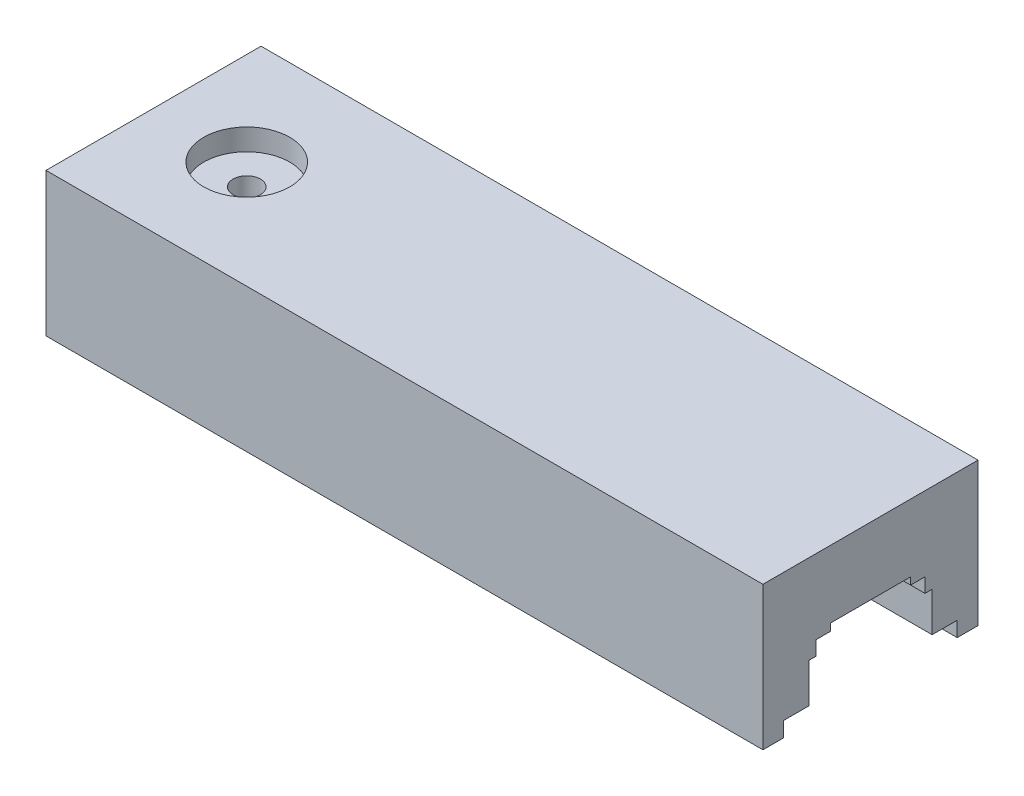
SolidWorks part; units mm, degrees
ref_plane "Front Plane" through (0, 0, 0) normal (0, 0, 1) x (1, 0, 0)
ref_plane "Top Plane" through (0, 0, 0) normal (0, 1, 0) x (1, 0, 0)
ref_plane "Right Plane" through (0, 0, 0) normal (1, 0, 0) x (0, 0, -1)
sketch "Sketch1" plane through (0, 0, 0) normal (0, 1, 0) x (1, 0, 0)
  line L1 (0, 15) -> (100, 15)
  line L2 (0, 15) -> (0, -15)
  line L3 (0, -15) -> (100, -15)
  line L4 (100, 15) -> (100, -15)
  point P4 (0, 0)
  dimension "D1" = 30
  dimension "D2" = 100
extrude "Boss-Extrude1" add sketch "Sketch1" along normal blind 20
sketch "Sketch2" plane through (100, 0, 0) normal (1, 0, 0) x (0, 0, -1)
  line L1 (-7.6, 0) -> (7.6, 0)
  line L2 (-7.6, 0) -> (-7.6, 9.6)
  line L3 (-7.6, 9.6) -> (7.6, 9.6)
  line L4 (7.6, 0) -> (7.6, 9.6)
  point P4 (0, 0)
  dimension "D1" = 15.2
  dimension "D2" = 9.6
extrude "Cut-Extrude1" cut sketch "Sketch2" against normal through all
sketch "Sketch3" plane through (100, 0, 0) normal (1, 0, 0) x (0, 0, -1)
  line L0 (-15, 20) -> (-15, 0) construction
  line L1 (-7.6, 0) -> (-12.1, 0)
  line L2 (-7.6, 0) -> (-7.6, 2.1)
  line L3 (-7.6, 2.1) -> (-12.1, 2.1)
  line L4 (-12.1, 0) -> (-12.1, 2.1)
  line L5 (7.6, 0) -> (15, 0) construction
  line L6 (12.1, 0) -> (7.6, 0)
  line L7 (12.1, 0) -> (12.1, 2.1)
  line L8 (12.1, 2.1) -> (7.6, 2.1)
  line L9 (7.6, 0) -> (7.6, 2.1)
  line L10 (7.6, 0) -> (7.6, 9.6) construction
  line L11 (15, 20) -> (15, 0) construction
  line L12 (7.6, 9.6) -> (-7.6, 9.6) construction
  line L13 (-7.6, 2.1) -> (-8.6, 2.1)
  line L14 (-7.6, 2.1) -> (-7.6, 7.6)
  line L15 (-7.6, 7.6) -> (-8.6, 7.6)
  line L16 (-8.6, 2.1) -> (-8.6, 7.6)
  line L17 (-7.6, 9.6) -> (-7.6, 0) construction
  line L18 (7.6, 2.1) -> (8.6, 2.1)
  line L19 (7.6, 2.1) -> (7.6, 7.6)
  line L20 (7.6, 7.6) -> (8.6, 7.6)
  line L21 (8.6, 2.1) -> (8.6, 7.6)
  line L22 (-5.6, 9.6) -> (5.6, 9.6)
  line L23 (-5.6, 9.6) -> (-5.6, 10.6)
  line L24 (-5.6, 10.6) -> (5.6, 10.6)
  line L25 (5.6, 9.6) -> (5.6, 10.6)
  line M1 (-15, 0) -> (-7.6, 0)
  line M2 (-7.6, 0) -> (-7.6, 9.6)
  line M3 (-7.6, 9.6) -> (7.6, 9.6)
  line M4 (7.6, 9.6) -> (7.6, 0)
  line M5 (7.6, 0) -> (15, 0)
  dimension "D1" = 2.1
  dimension "D2" = 2.9
  dimension "D3" = 2.9
  dimension "D4" = 2.1
  dimension "D5" = 1
  dimension "D6" = 2
  dimension "D7" = 1
  dimension "D8" = 2
  dimension "D9" = 1
  dimension "D10" = 2
  dimension "D11" = 2
extrude "Cut-Extrude2" cut sketch "Sketch3" against normal through all contours L16 L3 L15 M2 | L8 L21 L20 M4 | L7 L8 M4 M5 | L4 L3 M1 M2 | L25 L24 L23 M3 region at (100, 4.85, -8.1) region at (100, 10.1, 0) region at (100, 1.05, 9.85) region at (100, 4.85, 8.1) region at (100, 1.05, -9.85)
sketch "Sketch4" plane through (0, 0, 0) normal (0, -1, 0) x (1, 0, 0)
  line L0 (0, 12.1) -> (100, 12.1) construction
  line L1 (0, -12.1) -> (5, -12.1)
  line L2 (0, -12.1) -> (0, 12.1)
  line L3 (0, 12.1) -> (5, 12.1)
  line L4 (5, -12.1) -> (5, 12.1)
  dimension "D1" = 5
extrude "Boss-Extrude2" add sketch "Sketch4" against normal up to next
sketch "Sketch6" plane through (0, 0, 0) normal (0, -1, 0) x (1, 0, 0)
  line L0 (5, -12.1) -> (100, -12.1) construction
  line L1 (5, 12.1) -> (2.9, 12.1)
  line L2 (5, 12.1) -> (5, -12.1)
  line L3 (5, -12.1) -> (2.9, -12.1)
  line L4 (2.9, 12.1) -> (2.9, -12.1)
  line L5 (0, -15) -> (0, 15) construction
  dimension "D1" = 2.9
extrude "Cut-Extrude3" cut sketch "Sketch6" against normal up to surface (2.1 mm away) up to face at (52.5, 2.1, 10.35)
sketch "Sketch9" plane through (0, 9.6, 0) normal (0, -1, 0) x (1, 0, 0)
  line L0 (5, -5.6) -> (100, -5.6) construction
  line L1 (5, 5.6) -> (24.05, 5.6)
  line L2 (5, 5.6) -> (5, -5.6)
  line L3 (5, -5.6) -> (24.05, -5.6)
  line L4 (24.05, 5.6) -> (24.05, -5.6)
  dimension "D1" = 19.05
extrude "Boss-Extrude3" add sketch "Sketch9" against normal up to next
fillet "Fillet1" radius 1.5875 4 edges at (5, 4.85, -8.6) (5, 4.85, 8.6) (2.9, 1.05, -12.1) (2.9, 1.05, 12.1)
fillet "Fillet2" radius 1.5875 2 edges at (5.1127, 8.6, -7.6) (5.1127, 8.6, 7.6)
sketch "Sketch7" plane through (0, 9.6, 0) normal (0, -1, 0) x (1, 0, 0)
  line L1 (5, -6.0125) -> (5, 6.0125) construction
  circle A0 centre (13, 0) radius 1.905
  dimension "D1" = 3.81
  dimension "D2" = 8
extrude "Cut-Extrude4" cut sketch "Sketch7" against normal through all
sketch "Sketch10" plane through (0, 9.6, 0) normal (0, -1, 0) x (1, 0, 0)
  circle A0 centre (13, 0) radius 3.25
  circle A3 centre (13, 0) radius 1.905 construction
  dimension "D1" = 6.5
extrude "Cut-Extrude6" cut sketch "Sketch10" against normal blind 4
sketch "Sketch8" plane through (0, 20, 0) normal (0, 1, 0) x (1, 0, 0)
  circle A0 centre (13, 0) radius 6
  dimension "D1" = 12
extrude "Cut-Extrude5" cut sketch "Sketch8" against normal blind 3
fillet "Fillet5" radius 1.5875 2 edges at (24.05, 10.1, -5.6) (24.05, 10.1, 5.6)
